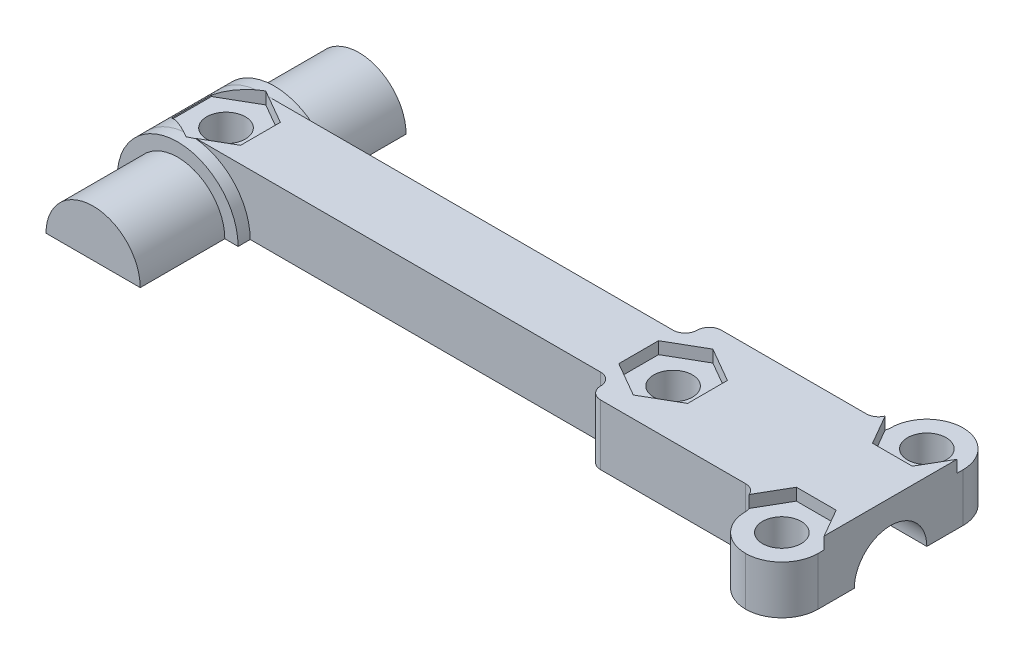
SolidWorks part; units mm, degrees
ref_plane "Front Plane" through (0, 0, 0) normal (0, 0, 1) x (1, 0, 0)
ref_plane "Top Plane" through (0, 0, 0) normal (0, 1, 0) x (1, 0, 0)
ref_plane "Right Plane" through (0, 0, 0) normal (1, 0, 0) x (0, 0, -1)
sketch "Sketch1" plane through (0, 0, 0) normal (0, 1, 0) x (1, 0, 0)
  line L1 (-5, -3) -> (5, -3)
  line L2 (-5, -3) -> (-5, 3)
  line L3 (-5, 3) -> (5, 3)
  line L4 (5, -3) -> (5, 3)
  line L5 (-5, -3) -> (5, 3) construction
  line L6 (-5, 3) -> (5, -3) construction
  point P0 (0, 0)
  dimension "D1" = 6
  dimension "D2" = 10
extrude "Boss-Extrude1" add sketch "Sketch1" along normal blind 5
sketch "Sketch2" plane through (0, 0, 3) normal (0, 0, 1) x (1, 0, 0)
  line L0 (-5, 0) -> (5, 0) construction
  line L1 (-5, 0) -> (5, 0)
  arc A0 (-5, 0) -> (5, 0) centre (0, 0) cw
  dimension "D1" = 10
extrude "Boss-Extrude3" add sketch "Sketch2" along normal blind 1
sketch "Sketch3" plane through (0, 0, 4) normal (0, 0, 1) x (1, 0, 0)
  line L0 (-5, 0) -> (5, 0) construction
  line L1 (-3.9, 0) -> (3.9, 0)
  arc A0 (-3.9, 0) -> (3.9, 0) centre (0, 0) cw
  dimension "D1" = 7.8
extrude "Boss-Extrude4" add sketch "Sketch3" along normal blind 7 contours A0 L1
ref_plane "Plane1" through (0, 0, 0) normal (0, 0, 1) x (1, 0, 0)
mirror "Mirror1" about plane through (0, 0, 0) normal (0, 0, 1) of "Boss-Extrude3", "Boss-Extrude4"
sketch "Sketch4" plane through (5, 0, 0) normal (1, 0, 0) x (0, 0, -1)
  line L1 (-3, 5) -> (3, 5)
  line L2 (-3, 5) -> (-3, 0)
  line L3 (-3, 0) -> (3, 0)
  line L4 (3, 5) -> (3, 0)
extrude "Boss-Extrude5" add sketch "Sketch4" along normal blind 30 contours L2 L3 L4 L1
sketch "Sketch5" plane through (0, 0, 0) normal (0, 1, 0) x (1, 0, 0)
  line L0 (35, -3) -> (35, 3) construction
  line L1 (35, 5) -> (49, 5)
  line L2 (35, 5) -> (35, -5)
  line L3 (35, -5) -> (49, -5)
  line L4 (49, 5) -> (49, -5)
  point P4 (35, 0)
  dimension "D1" = 10
  dimension "D2" = 14
extrude "Boss-Extrude6" add sketch "Sketch5" along normal blind 5
fillet "Fillet17" radius 5 1 edges at (-5, 5, 0)
sketch "Sketch8" plane through (49, 0, 0) normal (1, 0, 0) x (0, 0, -1)
  line L0 (-5, 5) -> (5, 5) construction
  line L1 (9, 5) -> (-9, 5)
  line L2 (9, 5) -> (9, 0)
  line L3 (9, 0) -> (-9, 0)
  line L4 (-9, 5) -> (-9, 0)
  dimension "D1" = 18
extrude "Boss-Extrude7" add sketch "Sketch8" along normal blind 6 contours L1 L4 L3 L2
fillet "Fillet8" radius 1 6 edges at (49, 2.5, 5) (35, 2.5, 5) (35, 2.5, 3) (35, 2.5, -3) (35, 2.5, -5) (49, 2.5, -5)
sketch "Sketch9" plane through (55, 0, 0) normal (1, 0, 0) x (0, 0, -1)
  line L0 (9, 0) -> (-9, 0) construction
  line L1 (-3, 0) -> (3, 0)
  arc A0 (-3, 0) -> (3, 0) centre (0, 0) cw
  dimension "D1" = 6
extrude "Cut-Extrude3" cut sketch "Sketch9" against normal blind 15
sketch "Sketch10" plane through (0, 0, 0) normal (0, -1, 0) x (1, 0, 0)
  line L0 (52, 9) -> (52, -9) construction
  line L1 (55, 9) -> (49, 9) construction
  line L2 (55, -9) -> (49, -9) construction
  line L3 (55, 0) -> (34.7071, 0) construction
  line L4 (55, -3) -> (55, 3) construction
  line L5 (40, -3) -> (40, 3) construction
  circle A0 centre (52, 6) radius 1.6
  circle A1 centre (52, -6) radius 1.6
  circle A2 centre (37, 0) radius 1.6
  circle A3 centre (0, 0) radius 1.6
  dimension "D1" = 3.2
  dimension "D2" = 3
  dimension "D3" = 3
  dimension "D4" = 3
extrude "Cut-Extrude4" cut sketch "Sketch10" against normal through all
fillet "Fillet11" radius 3 4 edges at (49, 2.5, -9) (55, 2.5, -9) (49, 2.5, 9) (55, 2.5, 9)
sketch "Sketch12" plane through (0, 5, 0) normal (0, 1, 0) x (1, 0, 0)
  circle A0 centre (0, 0) radius 3
  circle A1 centre (37, 0) radius 3
  circle A2 centre (52, -6) radius 3
  circle A3 centre (52, 6) radius 3
extrude "Cut-Extrude8" [suppressed] cut sketch "Sketch12" against normal blind 1
sketch "Sketch13" plane through (0, 5, 0) normal (0, 1, 0) x (1, 0, 0)
  line L1 (55.2909, -6) -> (53.6454, -3.15)
  line L2 (53.6454, -3.15) -> (50.3546, -3.15)
  line L3 (50.3546, -3.15) -> (48.7091, -6)
  line L4 (48.7091, -6) -> (50.3546, -8.85)
  line L5 (50.3546, -8.85) -> (53.6454, -8.85)
  line L6 (53.6454, -8.85) -> (55.2909, -6)
  line L7 (55.2909, 6) -> (53.6454, 8.85)
  line L8 (53.6454, 8.85) -> (50.3546, 8.85)
  line L9 (50.3546, 8.85) -> (48.7091, 6)
  line L10 (48.7091, 6) -> (50.3546, 3.15)
  line L11 (50.3546, 3.15) -> (53.6454, 3.15)
  line L12 (53.6454, 3.15) -> (55.2909, 6)
  line L13 (39.85, -1.6454) -> (39.85, 1.6454)
  line L14 (39.85, 1.6454) -> (37, 3.2909)
  line L15 (37, 3.2909) -> (34.15, 1.6454)
  line L16 (34.15, 1.6454) -> (34.15, -1.6454)
  line L17 (34.15, -1.6454) -> (37, -3.2909)
  line L18 (37, -3.2909) -> (39.85, -1.6454)
  line L19 (0, -3.2909) -> (2.85, -1.6454)
  line L20 (2.85, -1.6454) -> (2.85, 1.6454)
  line L21 (2.85, 1.6454) -> (0, 3.2909)
  line L22 (0, 3.2909) -> (-2.85, 1.6454)
  line L23 (-2.85, 1.6454) -> (-2.85, -1.6454)
  line L24 (-2.85, -1.6454) -> (0, -3.2909)
  circle A0 centre (52, -6) radius 2.85 construction
  circle A1 centre (52, 6) radius 2.85 construction
  circle A2 centre (37, 0) radius 2.85 construction
  circle A3 centre (0, 0) radius 2.85 construction
  dimension "D1" = 5.7
extrude "Cut-Extrude9" cut sketch "Sketch13" against normal blind 1
sketch "Sketch14" plane through (0, 5, 0) normal (0, 1, 0) x (1, 0, 0)
  line L0 (50.3546, -3.15) -> (48.9264, -5.6236) construction
  line L1 (55, -5.4962) -> (49, -5.4962)
  line L2 (55, -5.4962) -> (55, -10.4962)
  line L3 (55, -10.4962) -> (49, -10.4962)
  line L4 (49, -5.4962) -> (49, -10.4962)
  line L5 (55, 0) -> (32.9413, 0) construction
  line L6 (55, 5.4962) -> (55, -5.4962) construction
  line L7 (55, 10.4962) -> (49, 10.4962)
  line L8 (49, 5.4962) -> (49, 10.4962)
  line L9 (55, 5.4962) -> (49, 5.4962)
  line L10 (55, 5.4962) -> (55, 10.4962)
  dimension "D1" = 5
extrude "Cut-Extrude10" cut sketch "Sketch14" against normal up to surface (1 mm away) up to face at (51.9954, 4, 6.4108)
